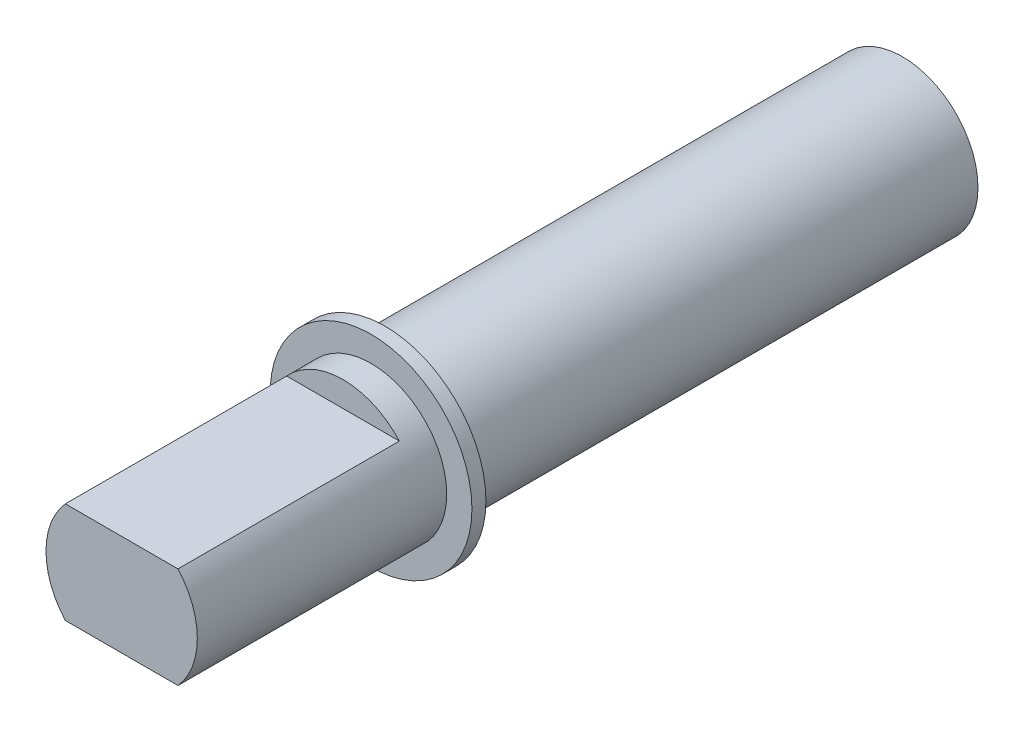
SolidWorks part; units mm, degrees
ref_plane "Front Plane" through (0, 0, 0) normal (0, 0, 1) x (1, 0, 0)
ref_plane "Top Plane" through (0, 0, 0) normal (0, 1, 0) x (1, 0, 0)
ref_plane "Right Plane" through (0, 0, 0) normal (1, 0, 0) x (0, 0, -1)
sketch "Sketch1" plane through (0, 0, 0) normal (0, 0, 1) x (1, 0, 0)
  circle A0 centre (0, 0) radius 2.7
  dimension "D1" = 5.4
extrude "Boss-Extrude1" add sketch "Sketch1" along normal mid plane 18.46
sketch "Sketch2" plane through (0, 0, 9.23) normal (0, 0, 1) x (1, 0, 0)
  circle A0 centre (0, 0) radius 3.6
  dimension "7.2" = 7.2
extrude "Boss-Extrude2" add sketch "Sketch2" along normal blind 0.5
sketch "Sketch3" plane through (0, 0, 9.73) normal (0, 0, 1) x (1, 0, 0)
  line L0 (-2.7, 0) -> (2.7, 0) construction
  line L1 (-2.01, 1.8027) -> (2.01, 1.8027)
  line L2 (-2.01, -1.8027) -> (2.01, -1.8027)
  circle A0 centre (0, 0) radius 2.7
  dimension "D1" = 5.4
  dimension "D2" = 4.02
  dimension "D3" = 4.02
extrude "Boss-Extrude3" add sketch "Sketch3" along normal blind 1 contours A0
extrude "Boss-Extrude4" add sketch "Sketch3<3>" along normal blind 8.9 contours A0 L0 L1 | L0 A0 L2 region at (0, 0.861, 9.73) region at (0, -0.861, 9.73)
sketch "Sketch3<3>" plane through (0, 0, 9.73) normal (0, 0, 1) x (1, 0, 0) same geometry as "Sketch3"
